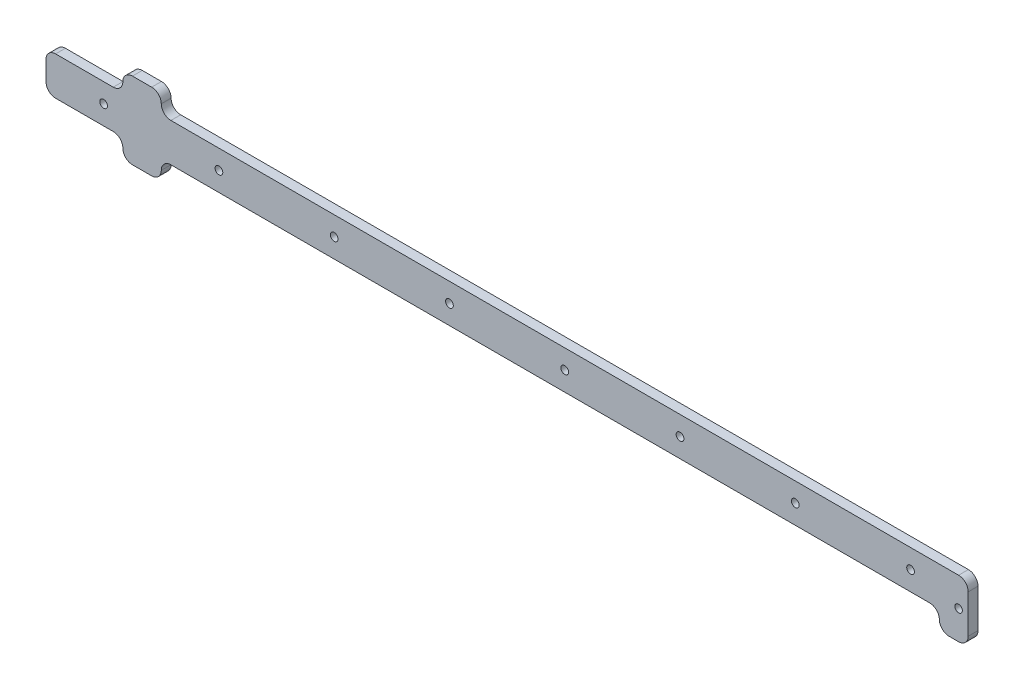
SolidWorks part; units mm, degrees
material "PC High Viscosity"
ref_plane "Front Plane" through (0, 0, 0) normal (0, 0, 1) x (1, 0, 0)
ref_plane "Top Plane" through (0, 0, 0) normal (0, 1, 0) x (1, 0, 0)
ref_plane "Right Plane" through (0, 0, 0) normal (1, 0, 0) x (0, 0, -1)
sketch "Sketch1" plane through (0, 0, 0) normal (0, 0, 1) x (1, 0, 0)
  line L0 (50.8, 0) -> (50.8, -12.7)
  line L1 (0, 0) -> (590.55, 0)
  line L2 (0, 0) -> (0, 25.4)
  line L3 (0, 25.4) -> (609.6, 25.4)
  line L4 (609.6, 0) -> (609.6, 25.4)
  line L5 (50.8, 38.1) -> (76.2, 38.1)
  line L6 (76.2, 38.1) -> (76.2, 25.4)
  line L7 (50.8, 38.1) -> (50.8, 25.4)
  line L8 (76.2, 0) -> (76.2, -12.7)
  line L9 (76.2, -12.7) -> (50.8, -12.7)
  line L10 (590.55, 0) -> (590.55, -12.7)
  line L11 (609.6, 10.0162) -> (603.25, 13.6823) construction
  line L12 (603.25, 13.6823) -> (596.9, 10.0162) construction
  line L13 (596.9, 10.0162) -> (596.9, 2.6838) construction
  line L14 (596.9, 2.6838) -> (603.25, -0.9823) construction
  line L15 (603.25, -0.9823) -> (609.6, 2.6838) construction
  line L16 (609.6, 2.6838) -> (609.6, 10.0162) construction
  line L17 (609.6, 0) -> (609.6, -12.7)
  line L18 (609.6, -12.7) -> (590.55, -12.7)
  circle A0 centre (603.25, 6.35) radius 2.4892
  circle A1 centre (603.25, 6.35) radius 6.35 construction
  dimension "D5" = 4.9784
  dimension "D6" = 12.7
  dimension "D7" = 12.7
  dimension "D1" = 609.6
  dimension "D2" = 25.4
  dimension "D3" = 25.4
  dimension "D4" = 50.8
  dimension "D8" = 19.05
  dimension "D9" = 12.7
extrude "Boss-Extrude1" add sketch "Sketch1" along normal blind 6.477 contours L6 L5 L3 | L1 L4 L3 L2 A0 | L9 L8 L1 region at (63.5, -6.35, 0) region at (308.9784, 12.4144, 0) region at (63.5, 31.75, 0)
fillet "Fillet2" radius 6.35 14 edges at (76.2, 38.1, 3.2385) (76.2, 25.4, 3.2385) (609.6, 25.4, 3.2385) (76.2, 0, 3.2385) (76.2, -12.7, 3.2385) (50.8, -12.7, 3.2385) (50.8, 0, 3.2385) (0, 0, 3.2385) (50.8, 38.1, 3.2385) (50.8, 25.4, 3.2385) (0, 25.4, 3.2385) (590.55, 0, 3.2385) (590.55, -12.7, 3.2385) (609.6, -12.7, 3.2385)
sketch "Sketch2" plane through (0, 0, 6.477) normal (0, 0, 1) x (1, 0, 0)
  line L0 (82.55, 25.4) -> (603.25, 25.4) construction
  line L1 (609.6, 19.05) -> (609.6, -6.35) construction
  circle A0 centre (571.5, 12.7) radius 2.0193
  dimension "D1" = 4.0386
  dimension "D2" = 12.7
  dimension "D3" = 38.1
hole_wizard "CSK for #10 Flat Head Machine Screw (100)1" positions "Sketch4" profile "Sketch5" countersink size "#10" standard "ANSI Inch" end condition through all
sketch "Sketch4" plane through (0, 0, 6.477) normal (0, 0, 1) x (1, 0, 0)
  line L0 (609.6, 12.7) -> (0, 12.7) construction
  line L1 (609.6, 19.05) -> (609.6, -6.35) construction
  line L2 (0, 6.35) -> (0, 19.05) construction
  line L3 (82.55, 25.4) -> (603.25, 25.4) construction
  point P11 (571.5, 12.7)
  dimension "D1" = 12.7
  dimension "D2" = 38.1
sketch "Sketch5" plane through (571.5, 12.7, 6.477) normal (1, 0, 0) x (0, -1, 0)
  line L0 (0, 0) -> (0, 6.477)
  line L1 (0, 6.477) -> (2.5527, 6.477)
  line L2 (2.5527, 6.477) -> (2.5527, 1.9608)
  line L3 (2.5527, 1.9608) -> (4.8895, 0)
  line L5 (4.8895, 0) -> (0, 0)
  line L6 (-2.5527, 1.9608) -> (-4.8895, 0) construction
  line L11 (0, -6.35) -> (0, 107.95) construction
  dimension "Thru Hole Dia." = 5.1054
  dimension "Thru Hole Depth" = 6.477
  dimension "Near C'Sink Dia." = 9.779
  dimension "Near C'Sink Angle" = 100
pattern_linear "LPattern1" count 8 spacing 76.2 along (-1, 0, 0) of "CSK for #10 Flat Head Machine Screw (100)1"
mirror "Mirror2" about plane through (0, 0, 0) normal (0, 0, 1) of bodies 108
delete or keep bodies "Body-Delete/Keep 1" type delete bodies bodies 108
